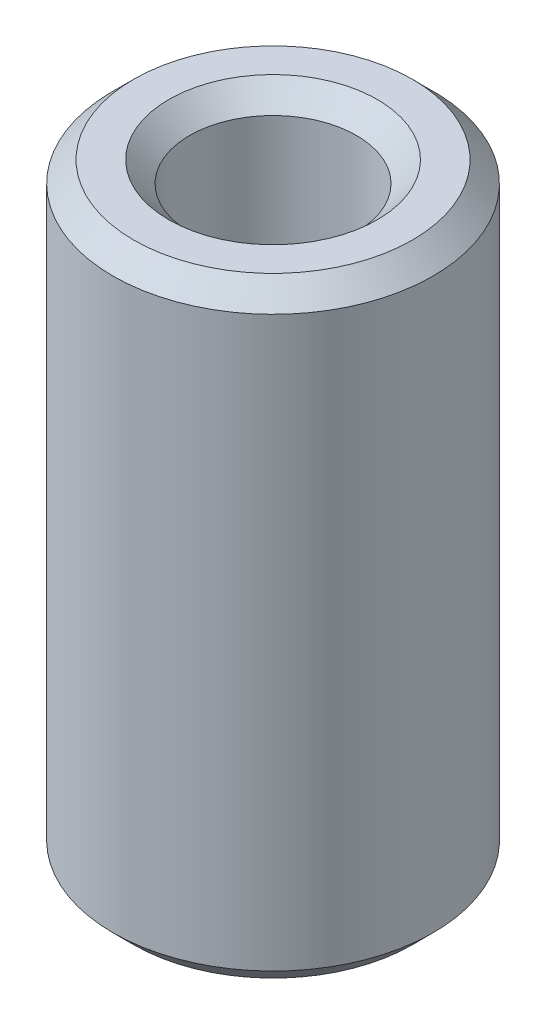
SolidWorks part; units mm, degrees
ref_plane "Front Plane" through (0, 0, 0) normal (0, 0, 1) x (1, 0, 0)
ref_plane "Top Plane" through (0, 0, 0) normal (0, 1, 0) x (1, 0, 0)
ref_plane "Right Plane" through (0, 0, 0) normal (1, 0, 0) x (0, 0, -1)
sketch "Sketch1" plane through (0, 0, 0) normal (0, 1, 0) x (1, 0, 0)
  circle A0 centre (0, 0) radius 20
  dimension "SLEEVE_OD" = 40
extrude "Boss-Extrude1" add sketch "Sketch1" along normal blind 76.2451
sketch "Sketch2" plane through (0, 0, 0) normal (0, 1, 0) x (1, 0, 0)
  circle A0 centre (0, 0) radius 10.428
  dimension "BORE_D" = 20.8561
extrude "Cut-Extrude1" cut sketch "Sketch2" along normal through all
chamfer "Chamfer1" distance 2.5948 angle 45 4 edges at (0, 76.2451, 10.428) (0, 0, 10.428) (0, 0, 20) (0, 76.2451, 20)
